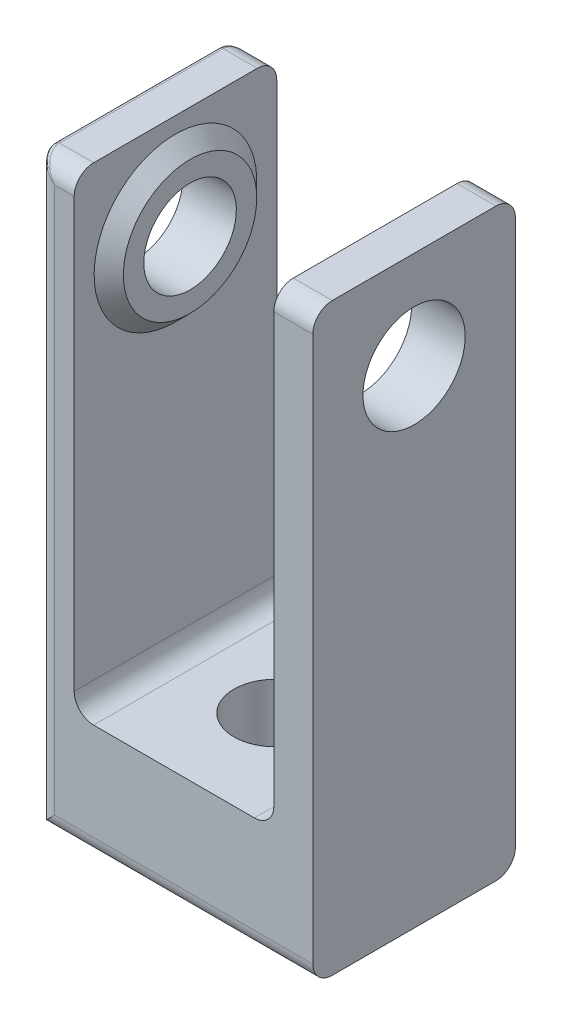
SolidWorks part; units mm, degrees
ref_plane "Front Plane" through (0, 0, 0) normal (0, 0, 1) x (1, 0, 0)
ref_plane "Top Plane" through (0, 0, 0) normal (0, 1, 0) x (1, 0, 0)
ref_plane "Right Plane" through (0, 0, 0) normal (1, 0, 0) x (0, 0, -1)
sketch "Sketch1" plane through (0, 0, 0) normal (0, 1, 0) x (1, 0, 0)
  line L1 (-7.125, 5.2) -> (7.125, 5.2)
  line L2 (-7.125, 5.2) -> (-7.125, -5.2)
  line L3 (-7.125, -5.2) -> (7.125, -5.2)
  line L4 (7.125, 5.2) -> (7.125, -5.2)
  line L5 (-7.125, 5.2) -> (7.125, -5.2) construction
  line L6 (-7.125, -5.2) -> (7.125, 5.2) construction
  point P0 (0, 0)
  dimension "D1" = 14.25
  dimension "D2" = 10.4
extrude "Boss-Extrude1" add sketch "Sketch1" along normal blind 30
sketch "Sketch2" plane through (0, 0, 5.2) normal (0, 0, 1) x (1, 0, 0)
  line L0 (7.125, 30) -> (-7.125, 30) construction
  line L1 (5.125, 30) -> (-5.125, 30)
  line L2 (5.125, 30) -> (5.125, 6)
  line L3 (5.125, 6) -> (-5.125, 6)
  line L4 (-5.125, 30) -> (-5.125, 6)
  line L5 (7.125, 0) -> (-7.125, 0) construction
  point P6 (0, 6)
  dimension "D1" = 6
  dimension "D2" = 10.25
extrude "Cut-Extrude1" cut sketch "Sketch2" against normal through all
sketch "Sketch3" plane through (-7.125, 0, 0) normal (-1, 0, 0) x (0, 0, 1)
  line L0 (0, 30) -> (0, 25) construction
  line L1 (-5.2, 30) -> (5.2, 30) construction
  circle A0 centre (0, 25) radius 2.625
  dimension "D1" = 5.25
  dimension "D2" = 5
extrude "Cut-Extrude2" cut sketch "Sketch3" against normal through all
sketch "Sketch9" plane through (0, 0, 0) normal (0, -1, 0) x (1, 0, 0)
  point P0 (0, 0)
hole_wizard "CBORE for M3 SHCS1" positions "Sketch9" profile "Sketch10" counterbore size "M3" standard "ANSI Metric" end condition through all
sketch "Sketch10" plane through (0, 0, 0) normal (1, 0, 0) x (0, 0, -1)
  line L0 (0, 0) -> (0, 30)
  line L1 (0, 30) -> (2.125, 30)
  line L3 (2.125, 30) -> (2.125, 0.5)
  line L4 (2.125, 0.5) -> (2.625, 0.5)
  line L5 (2.625, 0.5) -> (2.625, 0)
  line L7 (2.625, 0) -> (0, 0)
  line L11 (0, -6.35) -> (0, 107.95) construction
  dimension "Thru Hole Dia." = 4.25
  dimension "Thru Hole Depth" = 30
  dimension "C'Bore Dia." = 5.25
  dimension "C'Bore Depth" = 0.5
sketch "Sketch7" plane through (5.125, 0, 0) normal (-1, 0, 0) x (0, 0, 1)
  circle A0 centre (0, 25) radius 2.625
  circle A1 centre (0, 25) radius 3.425
  dimension "D1" = 0.8
extrude "Boss-Extrude2" add sketch "Sketch7" along normal blind 0.75
extrude "Boss-Extrude3" add sketch "Sketch7<2>" against normal blind 0.75 from surface starting at face at (-5.125, 22.375, 0)
sketch "Sketch7<2>" plane through (5.125, 0, 0) normal (-1, 0, 0) x (0, 0, 1) same geometry as "Sketch7"
sketch "Sketch8" plane through (-7.125, 0, 0) normal (-1, 0, 0) x (0, 0, 1)
  circle A0 centre (0, 25) radius 2.375
  circle A1 centre (0, 25) radius 2.625
  dimension "D1" = 4.75
extrude "Boss-Extrude4" add sketch "Sketch8" against normal up to surface (2.75 mm away) up to face at (-4.375, 22.375, 0)
chamfer "Chamfer1" distance 0.75 angle 45 2 edges at (-5.125, 21.575, 0) (5.125, 28.425, 0)
fillet "Fillet5" radius 0.25 1 edges at (-7.125, 30, 0)
fillet "Fillet4" radius 1 12 edges at (0, 0, 5.2) (0, 0, -5.2) (6.125, 30, 5.2) (6.125, 30, -5.2) (5.125, 6, 0) (-5.125, 6, 0) (-6, 30, -5.2) (-6, 30, 5.2) (-7.125, 14.875, -5.2) (-7.0518, 29.9268, -5.2) (-7.125, 14.875, 5.2) (-7.0518, 29.9268, 5.2)
